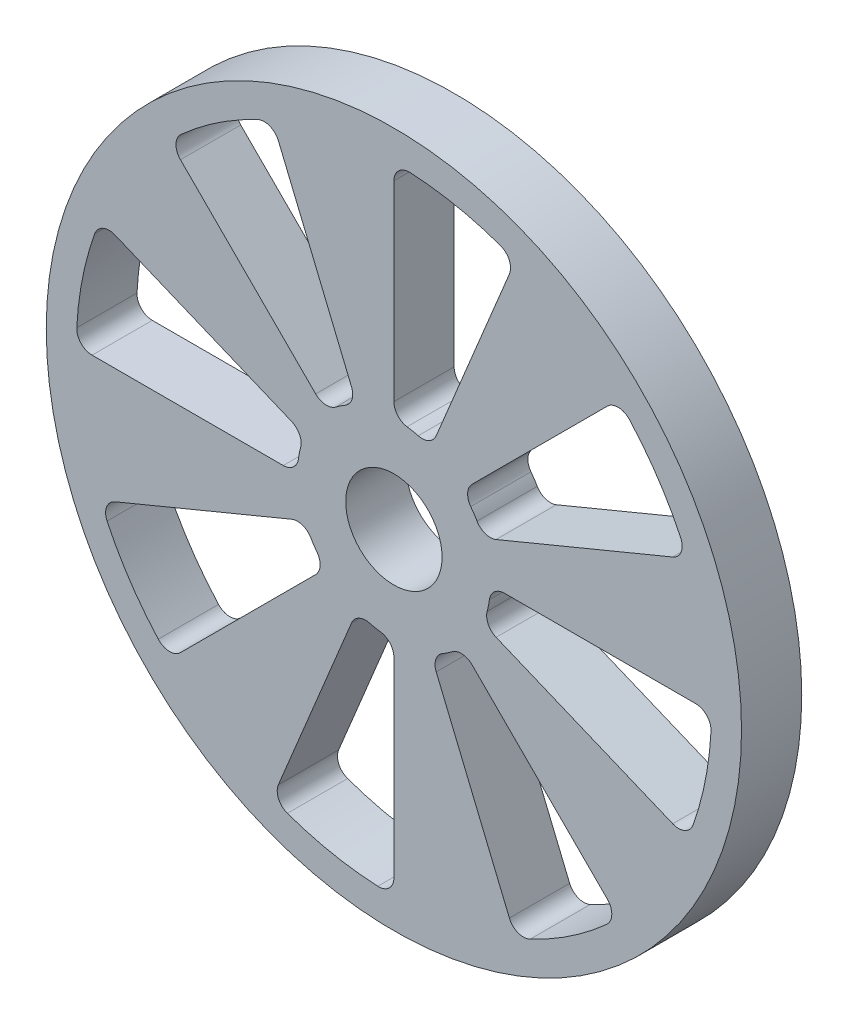
SolidWorks part; units mm, degrees
ref_plane "Front Plane" through (0, 0, 0) normal (0, 0, 1) x (1, 0, 0)
ref_plane "Top Plane" through (0, 0, 0) normal (0, 1, 0) x (1, 0, 0)
ref_plane "Right Plane" through (0, 0, 0) normal (1, 0, 0) x (0, 0, -1)
sketch "Sketch1" plane through (0, 0, 0) normal (0, 0, 1) x (1, 0, 0)
  line L0 (0, 8) -> (0, 26.355)
  line L1 (3.0615, 7.391) -> (10.0856, 24.3488)
  line L2 (5.6569, 5.6569) -> (18.6358, 18.6358)
  line L3 (7.391, 3.0615) -> (24.3488, 10.0856)
  line L4 (8, 0) -> (26.355, 0)
  line L5 (7.391, -3.0615) -> (24.3488, -10.0856)
  line L6 (5.6569, -5.6569) -> (18.6358, -18.6358)
  line L7 (3.0615, -7.391) -> (10.0856, -24.3488)
  line L8 (0, -8) -> (0, -26.355)
  line L9 (-3.0615, -7.391) -> (-10.0856, -24.3488)
  line L10 (-5.6569, -5.6569) -> (-18.6358, -18.6358)
  line L11 (-7.391, -3.0615) -> (-24.3488, -10.0856)
  line L12 (-8, 0) -> (-26.355, 0)
  line L13 (-7.391, 3.0615) -> (-24.3488, 10.0856)
  line L14 (-5.6569, 5.6569) -> (-18.6358, 18.6358)
  line L15 (-3.0615, 7.391) -> (-10.0856, 24.3488)
  circle A0 centre (0, 0) radius 28.855
  circle A1 centre (0, 0) radius 26.355
  circle A2 centre (0, 0) radius 8
  circle A3 centre (0, 0) radius 4
  point P41 (0, 0)
  dimension "D1" = 57.71
  dimension "D2" = 52.71
  dimension "D3" = 16
  dimension "D4" = 8
  dimension "D5" = 16
extrude "Boss-Extrude1" add sketch "Sketch1" along normal blind 5 contours A0 A1 | A2 L0 A1 L15 | A2 L2 A1 L1 | A2 L4 A1 L3 | A2 L6 A1 L5 | A2 L8 A1 L7 | A2 L10 A1 L9 | A2 L12 A1 L11 | A2 L14 A1 L13 | A2 A3 region at (-3.6465, 18.3321, 0) region at (1.5166, 7.6244, 0) region at (10.3843, 15.5412, 0) region at (-15.5412, 10.3843, 0) region at (18.3321, 3.6465, 0) region at (-18.3321, -3.6465, 0) region at (15.5412, -10.3843, 0) region at (-10.3843, -15.5412, 0) region at (3.6465, -18.3321, 0) region at (-28.0389, 0, 0)
fillet "Fillet2" radius 1.27 32 edges at (-3.0615, 7.391, 2.5) (-7.391, -3.0615, 2.5) (-7.391, 3.0615, 2.5) (-5.6569, -5.6569, 2.5) (0, -8, 2.5) (-3.0615, -7.391, 2.5) (5.6569, 5.6569, 2.5) (7.391, -3.0615, 2.5) (3.0615, -7.391, 2.5) (5.6569, -5.6569, 2.5) (18.6358, -18.6358, 2.5) (26.355, 0, 2.5) (0, 8, 2.5) (8, 0, 2.5) (10.0856, -24.3488, 2.5) (-10.0856, -24.3488, 2.5) (-26.355, 0, 2.5) (-18.6358, 18.6358, 2.5) (0, 26.355, 2.5) (18.6358, 18.6358, 2.5) (7.391, 3.0615, 2.5) (3.0615, 7.391, 2.5) (-5.6569, 5.6569, 2.5) (-8, 0, 2.5) (-18.6358, -18.6358, 2.5) (0, -26.355, 2.5) (24.3488, -10.0856, 2.5) (24.3488, 10.0856, 2.5) (10.0856, 24.3488, 2.5) (-10.0856, 24.3488, 2.5) (-24.3488, 10.0856, 2.5) (-24.3488, -10.0856, 2.5)
